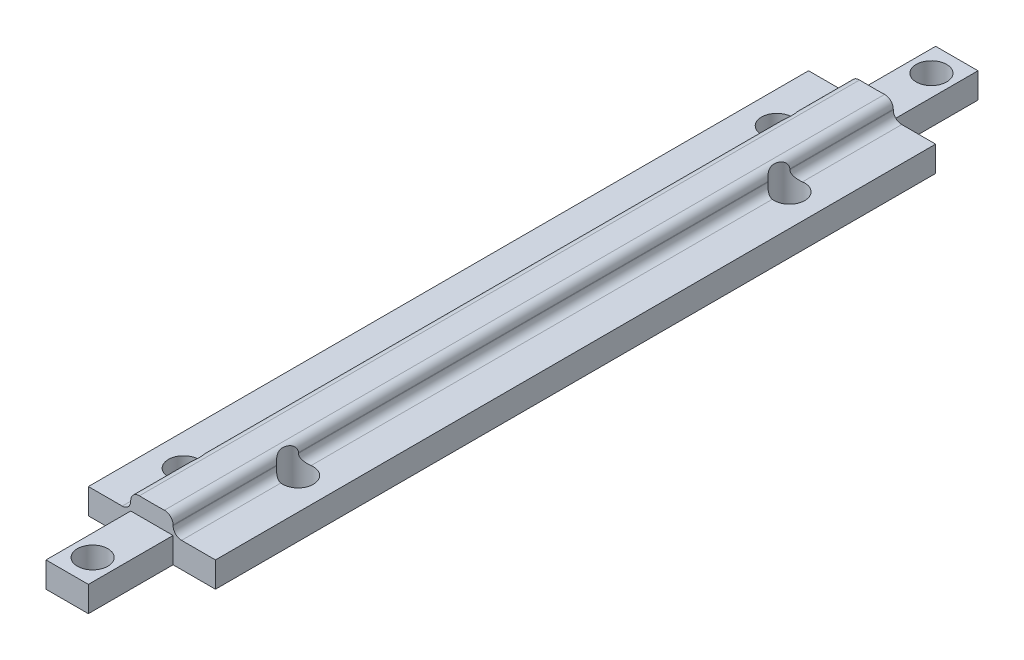
SolidWorks part; units mm, degrees
ref_plane "Front Plane" through (0, 0, 0) normal (0, 0, 1) x (1, 0, 0)
ref_plane "Top Plane" through (0, 0, 0) normal (0, 1, 0) x (1, 0, 0)
ref_plane "Right Plane" through (0, 0, 0) normal (1, 0, 0) x (0, 0, -1)
sketch "Sketch1" plane through (0, 0, 0) normal (0, 1, 0) x (1, 0, 0)
  line L1 (-2.5, -42.5) -> (2.5, -42.5)
  line L2 (-2.5, -42.5) -> (-2.5, 42.5)
  line L3 (-2.5, 42.5) -> (2.5, 42.5)
  line L4 (2.5, -42.5) -> (2.5, 42.5)
  line L5 (-2.5, -42.5) -> (2.5, 42.5) construction
  line L6 (-2.5, 42.5) -> (2.5, -42.5) construction
  point P0 (0, 0)
  dimension "D1" = 5
  dimension "D2" = 85
extrude "Boss-Extrude1" add sketch "Sketch1" along normal blind 3
ref_plane "Plane3" through (0, 0, 0) normal (0, 0, 1) x (1, 0, 0)
sketch "Sketch3" plane through (0, 0, 0) normal (0, 0, 1) x (1, 0, 0)
  line L0 (-2.5, 3) -> (-2.5, 5.103)
  line L1 (-2.5, 5.103) -> (2.5, 5.103) construction
  line L2 (2.5, 5.103) -> (2.5, 3)
  line L3 (0, 5.103) -> (0, 64.05) construction
  line L4 (-2.5, 0) -> (2.5, 0)
  line L5 (2.5, 0) -> (2.5, 3)
  line L6 (2.5, 3) -> (-2.5, 3)
  line L7 (-2.5, 3) -> (-2.5, 0)
  line L8 (-2.5, 0) -> (2.5, 0)
  line L9 (2.5, 0) -> (2.5, 3)
  line L11 (-2.5, 3) -> (-2.5, 0)
  arc A0 (-2.5, 5.103) -> (2.5, 5.103) centre (0, 64.05) ccw
  dimension "D1" = 0
extrude "Boss-Extrude2" add sketch "Sketch3" along normal up to surface (42.5 mm away) up to face at (0, 1.5, 42.5)
sketch "Sketch7" plane through (0, 0, 0) normal (0, 0, -1) x (-1, 0, 0)
  line L3 (-2.5, 5.103) -> (-2.5, 3)
  line L4 (-2.5, 3) -> (2.5, 3)
  line L5 (2.5, 3) -> (2.5, 5.103)
  line L6 (-2.5, 5.103) -> (-2.5, 3)
  line L7 (-2.5, 3) -> (2.5, 3)
  line L8 (2.5, 3) -> (2.5, 5.103)
  arc A1 (-2.5, 5.103) -> (2.5, 5.103) centre (0, 64.05) ccw
  arc A2 (-2.5, 5.103) -> (2.5, 5.103) centre (0, 64.05) ccw
  dimension "D1" = 0
extrude "Boss-Extrude3" add sketch "Sketch7" along normal up to surface (42.5 mm away) up to face at (0, 1.5, -42.5)
sketch "Sketch8" plane through (0, 0, 0) normal (0, -1, 0) x (1, 0, 0)
  line L0 (2.5, 42.5) -> (2.5, -42.5) construction
  line L1 (-2.5, 42.5) -> (2.5, 42.5)
  line L2 (-2.5, 42.5) -> (-2.5, 52.5)
  line L3 (-2.5, 52.5) -> (2.5, 52.5)
  line L4 (2.5, 42.5) -> (2.5, 52.5)
  line L5 (0, 0) -> (17.0745, 0) construction
  line L6 (-2.5, -52.5) -> (2.5, -52.5)
  line L7 (2.5, -42.5) -> (2.5, -52.5)
  line L8 (-2.5, -42.5) -> (2.5, -42.5)
  line L9 (-2.5, -42.5) -> (-2.5, -52.5)
  dimension "D1" = 10
extrude "Boss-Extrude4" add sketch "Sketch8" against normal blind 3
sketch "Sketch6" plane through (0, 3, 0) normal (0, 1, 0) x (1, 0, 0)
  line L0 (0, -52.5) -> (0, -49.5) construction
  line L2 (0, 0) -> (12.4428, 0) construction
  line L3 (-5.6053, 0) -> (5.6053, 0) construction
  line L4 (2.5, -52.5) -> (-2.5, -52.5) construction
  circle A0 centre (0, -49.5) radius 1.8
  circle A1 centre (0, 49.5) radius 1.8
  dimension "D1" = 3.6
  dimension "D2" = 3
extrude "Cut-Extrude1" cut sketch "Sketch6" against normal through all
sketch "Sketch9" plane through (0, 0, 0) normal (0, -1, 0) x (1, 0, 0)
  line L0 (2.5, -42.5) -> (-2.5, -42.5) construction
  line L1 (-2.5, 42.5) -> (2.5, 42.5) construction
  line L2 (2.5, -42.5) -> (-2.5, -42.5) construction
  line L3 (-2.5, 42.5) -> (2.5, 42.5) construction
  line L4 (-2.5, -52.5) -> (-2.5, 52.5) construction
  line L5 (-7.5, -42.5) -> (7.5, -42.5)
  line L6 (-7.5, -42.5) -> (-7.5, 42.5)
  line L7 (-7.5, 42.5) -> (7.5, 42.5)
  line L8 (7.5, -42.5) -> (7.5, 42.5)
  line L9 (-2.5, -52.5) -> (-2.5, 52.5) construction
  point P8 (0, -42.5)
  point P9 (0, -42.5)
  point P10 (0, 42.5)
  point P11 (0, 42.5)
  dimension "D1" = 5
extrude "Boss-Extrude5" add sketch "Sketch9" against normal up to surface (3 mm away) up to face at (0, 3, 51.3)
fillet "Fillet1" radius 1 4 edges at (-2.5, 5.103, 0) (2.5, 5.103, 0) (2.5, 3, 0) (-2.5, 3, 0)
sketch "Sketch10" plane through (0, 3, 0) normal (0, 1, 0) x (1, 0, 0)
  line L0 (0, -42.5) -> (0, -35) construction
  line L1 (-1.475, -42.5) -> (1.475, -42.5) construction
  line L2 (0, -35) -> (-3.75, -35) construction
  line L3 (-3.75, -35) -> (-7.5, -35) construction
  line L4 (-7.5, -42.5) -> (-7.5, 42.5) construction
  line L5 (0, -35) -> (0, -29) construction
  line L6 (0, -29) -> (3.75, -29) construction
  line L7 (3.75, -29) -> (7.5, -29) construction
  line L8 (7.5, 42.5) -> (7.5, -42.5) construction
  line L9 (-3.5, -42.5) -> (-7.5, -42.5) construction
  line L10 (-7.5, 0) -> (7.5, 0) construction
  circle A0 centre (-3.75, -35) radius 1.8
  circle A1 centre (3.75, -29) radius 1.8
  circle A2 centre (3.75, 29) radius 1.8
  circle A3 centre (-3.75, 35) radius 1.8
  dimension "D1" = 3.6
  dimension "D2" = 6
  dimension "D3" = 7.5
extrude "Cut-Extrude2" cut sketch "Sketch10" against normal through all both and the other way through all
